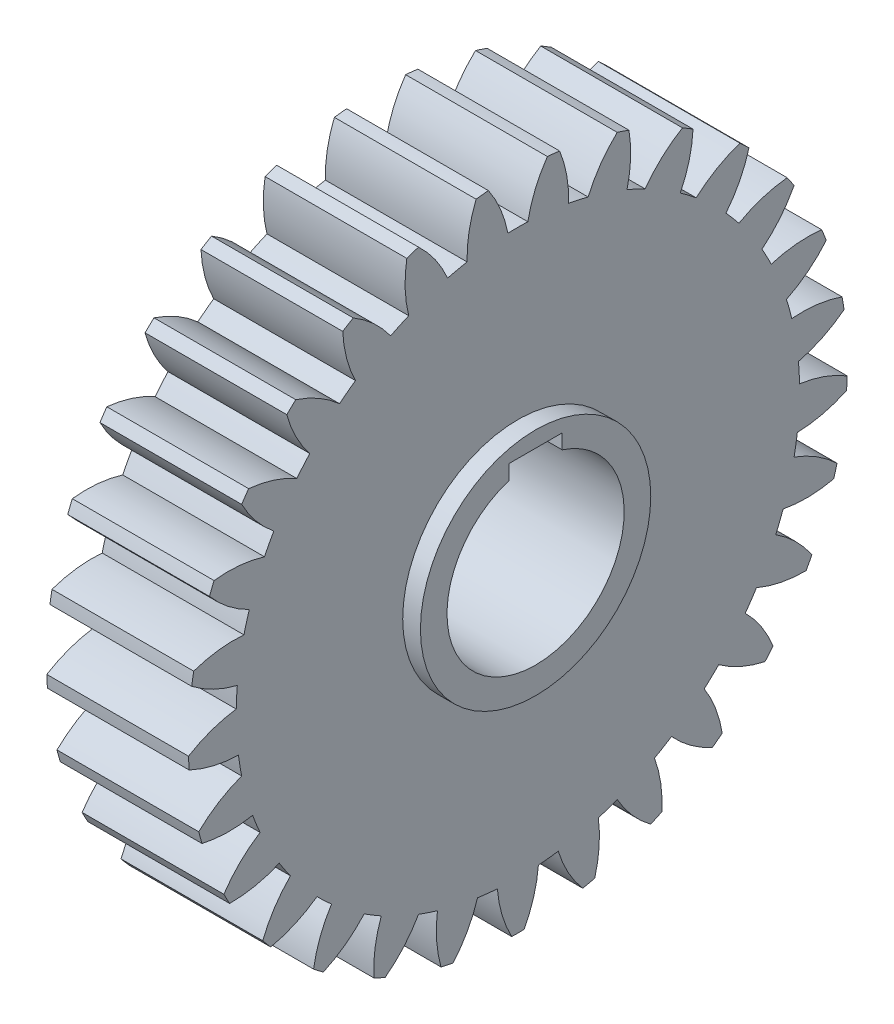
SolidWorks part; units mm, degrees
ref_plane "Plane1" through (0, 0, 0) normal (0, 0, 1) x (1, 0, 0)
ref_plane "Plane2" through (0, 0, 0) normal (0, 1, 0) x (1, 0, 0)
ref_plane "Plane3" through (0, 0, 0) normal (1, 0, 0) x (0, 0, -1)
sketch "HoldingSke" plane through (0, 0, 0) normal (0, 1, 0) x (1, 0, 0)
  line L0 (0, 0) -> (1.4577, -0.808)
  line L1 (-15, 0) -> (100, 0) construction
  line L2 (0, 0) -> (-2.1039, 2.3779)
  line L3 (0, 0) -> (-11.863, 4.5341)
  line L4 (0, 0) -> (7.5532, 4.1868)
  line L5 (0, 0) -> (-46.8476, -17.4728)
  line L6 (0, 0) -> (-3.3159, -2.2372)
  line L7 (-2.1039, 2.3779) -> (8.6586, 51.2059)
  line L8 (-76.2, 54.61) -> (-75.3, 54.61)
  line L9 (-71.009, 38.7566) -> (-53.1078, 45.2721)
  line L10 (-76.2, 71.12) -> (104.1128, 71.12)
  line L11 (0, 0) -> (-4, 0)
  line L12 (-76.2, 101.6) -> (-76.177, 101.6)
  line L13 (24.9733, 27.94) -> (52.9518, 28.4284)
  line L14 (24.9733, 27.94) -> (24.9743, 27.94)
  line L15 (24.9733, 27.94) -> (100.4006, 29.5858)
  line L16 (-63.627, -0.6) -> (-12.827, -0.6)
  circle A0 centre (0, 0) radius 2.5
  circle A1 centre (0, 0) radius 7.949
  circle A2 centre (0, 0) radius 37.5
  circle A3 centre (0, 0) radius 2.5
  dimension "MHD" = 15.898
  dimension "Hub_dia" = 75
  dimension "Bore" = 5
  dimension "MBD" = 5
  dimension "Num_teeth" = 29
  dimension "Pitch_radius" = 180.3128
  dimension "Pitch" = 1.6667
  dimension "Width" = 4
  dimension "Overall_len" = 50
  dimension "Show_teeth" = 29
  dimension "Thickness" = 4
  dimension "OAL" = 50.0001
  dimension "T_dim" = 0.9
  dimension "Ap" = 20
  dimension "H" = 19.05
  dimension "Backlash" = 0.023
  dimension "Addendum_fac" = 1
  dimension "Dedendum_fac" = 1.25
  dimension "Clearance_fac" = 0.25
  dimension "Dedendum_add" = 0.001
  dimension "Module" = 0.6
sketch "BasProSke" plane through (0, 0, 0) normal (0, 1, 0) x (1, 0, 0)
  line L0 (-10, 0) -> (60, 0) construction
  line L1 (0, 0) -> (0, 9.3)
  line L2 (0, 0) -> (4, 0)
  line L3 (4, 0) -> (4, 9.3)
  line L4 (4, 9.3) -> (0, 9.3)
  dimension "Diameter" = 18.6
  dimension "Thickness" = 4
revolve "Base-Revolve" add sketch "BasProSke" angle 360 about L0
sketch "TooCutSke" plane through (0, 0, 0) normal (1, 0, 0) x (0, 0, -1)
  line L1 (0, 0) -> (0, 107) construction
  line L2 (0, 0) -> (-0.5112, 8.685) construction
  line L3 (0, 0) -> (-1.879, 17.2768) construction
  line L4 (-0.5112, 8.685) -> (-0.9395, 8.6384) construction
  arc A0 (0.2815, 7.944) -> (-0.2815, 7.944) centre (0, 0) ccw
  arc A1 (0.8491, 9.2867) -> (-0.8491, 9.2867) centre (0, 0) ccw
  circle A2 centre (0, 0) radius 8.7 construction
  circle A3 centre (0, 0) radius 8.1753 construction
  arc A4 (-0.2815, 7.944) -> (-0.8491, 9.2867) centre (-3.6996, 7.2903) ccw
  arc A5 (0.8491, 9.2867) -> (0.2815, 7.944) centre (3.6996, 7.2903) ccw
  dimension "Root_dia" = 15.898
  dimension "Overcut_dia" = 18.6508
  dimension "Pitch_dia" = 17.4
  dimension "Base_dia" = 16.3507
  dimension "Flank_rad" = 3.48
  dimension "Half_ang" = 6.207
  dimension "Half_CT" = 0.4308
extrude "ToothCut" cut sketch "TooCutSke" along normal through all
fillet "Breaks" [suppressed] radius 0.012 tangent propagation no
fillet "RootFillets" [suppressed] radius 0.151
pattern_circular "TeethCuts" count 29 every 12.414 about axis through (-10, 0, 0) along (1, 0, 0) of "ToothCut", "RootFillets", "Breaks"
sketch "HubNeaOneSke" plane through (0, 0, 0) normal (-1, 0, 0) x (0, 0, 1)
  circle A0 centre (0, 0) radius 7.949
  dimension "Diameter" = 15.898
extrude "HubNearOne" [suppressed] add sketch "HubNeaOneSke" along normal blind 46.0001
sketch "HubNeaBotSke" plane through (0, 0, 0) normal (-1, 0, 0) x (0, 0, 1)
  circle A0 centre (0, 0) radius 7.949
  dimension "Diameter" = 15.898
extrude "HubNearBoth" [suppressed] add sketch "HubNeaBotSke" along normal blind 23
ref_plane "FarPln" through (4, 0, 0) normal (1, 0, 0) x (0, 0, -1)
sketch "HubFarSke" plane through (4, 0, 0) normal (1, 0, 0) x (0, 0, -1)
  circle A0 centre (0, 0) radius 7.949
  dimension "Diameter" = 15.898
extrude "HubFar" [suppressed] add sketch "HubFarSke" along normal blind 23
sketch "BorSke" plane through (0, 0, 0) normal (1, 0, 0) x (0, 0, -1)
  circle A0 centre (0, 0) radius 2.5
  dimension "Diameter" = 5
extrude "Bore" cut sketch "BorSke" along normal mid plane 100.0001
sketch "KeySke" plane through (0, 0, 0) normal (1, 0, 0) x (0, 0, -1)
  line L0 (-1, 0) -> (-1, 3.4)
  line L1 (-1, 3.4) -> (1, 3.4)
  line L2 (1, 3.4) -> (1, 0)
  line L3 (0, 0) -> (0, 34) construction
  line L4 (-1, 0) -> (1, 0)
  dimension "Offset" = 3.4
  dimension "Width" = 2
extrude "Keyway" [suppressed] cut sketch "KeySke" along normal mid plane 100.0001
pattern_circular "Keyway2" [suppressed] count 2 every 90 about axis through (-10, 0, 0) along (1, 0, 0)
sketch "Sketch1" plane through (0, 0, 0) normal (1, 0, 0) x (0, 0, -1)
  circle A0 centre (0, 0) radius 3.25
  circle A1 centre (0, 0) radius 2.5 construction
  circle A2 centre (0, 0) radius 2.5
  dimension "D1" = 6.5
extrude "Extrude1" add sketch "Sketch1" along normal blind 4.5 and the other way blind 0.5
sketch "Sketch2" plane through (0, 0, 0) normal (1, 0, 0) x (0, 0, -1)
  line L0 (0, 3.5365) -> (0, -1.3362) construction
  line L1 (-0.75, 2.8) -> (0.75, 2.8)
  line L2 (-0.75, 2.8) -> (-0.75, 0)
  line L3 (-0.75, 0) -> (0.75, 0)
  line L4 (0.75, 2.8) -> (0.75, 0)
  dimension "D1" = 2.8
  dimension "D2" = 1.5
extrude "Cut-Extrude1" cut sketch "Sketch2" against normal through all and the other way blind 20
equation "' \"Module@HoldingSke\" = 6.35"
equation "' \"Num_teeth@HoldingSke\" = 12"
equation "' \"Ap@HoldingSke\" =  20"
equation "' \"Width@HoldingSke\" = 0.5 * 25.4"
equation "' \"Hub_dia@HoldingSke\"= 1 * 25.4"
equation "' \"Overall_len@HoldingSke\" = 1.0 * 25.4"
equation "' \"Bore@HoldingSke\" = 0.75 * 25.4"
equation "' \"T_dim@HoldingSke\" = 0.1 * 25.4"
equation "' \"Width@KeySke\" = 0.25 * 25.4"
equation "' \"Show_teeth@HoldingSke\" = 13"
equation "' \"Backlash@HoldingSke\" = 0.009 * 25.4"
equation "' \"Addendum_fac@HoldingSke\" = 1.0"
equation "' \"Dedendum_fac@HoldingSke\" = 1.25"
equation "' \"Dedendum_add@HoldingSke\" = 0.00005 * 25.4"
equation "' \"Clearance_fac@HoldingSke\" = 0.25"
equation "\"Pitch@HoldingSke\" = 1 / \"Module@HoldingSke\""
equation "\"Overcut_dia@TooCutSke\" = (\"Num_teeth@HoldingSke\" + 2 * \"Addendum_fac@HoldingSke\") / \"Pitch@HoldingSke\" + 0.002 * 25.4"
equation "\"Pitch_dia@TooCutSke\" = \"Num_teeth@HoldingSke\" / \"Pitch@HoldingSke\""
equation "\"Base_dia@TooCutSke\" = \"Num_teeth@HoldingSke\" / \"Pitch@HoldingSke\" * cos((\"Ap@HoldingSke\"  * 3.14159265 / 180))"
equation "\"Root_dia@TooCutSke\" = (\"Num_teeth@HoldingSke\" + 2) / \"Pitch@HoldingSke\" - 2 * (\"Addendum_fac@HoldingSke\" + \"Dedendum_fac@HoldingSke\") / \"Pitch@HoldingSke\" - \"Dedendum_add@HoldingSke\" * 2"
equation "\"Half_ang@TooCutSke\" = 180 / \"Num_teeth@HoldingSke\""
equation "\"Half_CT@TooCutSke\" = \"Num_teeth@HoldingSke\" / \"Pitch@HoldingSke\" * sin((3.14159265 / 2 / \"Num_teeth@HoldingSke\")) / 2 - 7 * \"Backlash@HoldingSke\" / 4"
equation "\"Flank_rad@TooCutSke\" = \"Num_teeth@HoldingSke\" / \"Pitch@HoldingSke\" / 5"
equation "\"Radius@RootFillets\" = \"Clearance_fac@HoldingSke\" / \"Pitch@HoldingSke\" + \"Dedendum_add@HoldingSke\""
equation "\"Break_rad@Breaks\" = 0.02 / \"Pitch@HoldingSke\""
equation "\"Thickness@HoldingSke\" = \"Width@HoldingSke\""
equation "\"OAL@HoldingSke\" = \"Thickness@HoldingSke\""
equation "\"MHD@HoldingSke\" = (\"Num_teeth@HoldingSke\" + 2) / \"Pitch@HoldingSke\" - 2 * (\"Addendum_fac@HoldingSke\" + \"Dedendum_fac@HoldingSke\")  / \"Pitch@HoldingSke\" - \"Dedendum_add@HoldingSke\" * 2"
equation "\"MBD@HoldingSke\" = (\"Num_teeth@HoldingSke\" + 2) / \"Pitch@HoldingSke\" - 2 * (\"Addendum_fac@HoldingSke\" + \"Dedendum_fac@HoldingSke\")  / \"Pitch@HoldingSke\" - \"Dedendum_add@HoldingSke\" * 2 - 0.002 * 25.4"
equation "\"MHD@HoldingSke\" = ((sgn( \"MHD@HoldingSke\" - \"Hub_dia@HoldingSke\" )-1)*( \"MHD@HoldingSke\" - \"Hub_dia@HoldingSke\" ))/-2+ \"Hub_dia@HoldingSke\""
equation "\"MBD@HoldingSke\" = ((sgn( \"MBD@HoldingSke\" - \"Bore@HoldingSke\" )-1)*( \"MBD@HoldingSke\" - \"Bore@HoldingSke\" ))/-2+ \"Bore@HoldingSke\""
equation "\"OAL@HoldingSke\" = ((sgn( \"OAL@HoldingSke\" - \"Overall_len@HoldingSke\" )+1)*( \"OAL@HoldingSke\" - \"Overall_len@HoldingSke\" ))/2 + \"Overall_len@HoldingSke\" + 0.000002 * 25.4"
equation "\"Num_teeth@TeethCuts\" = int( \"Show_teeth@HoldingSke\" ) + 1"
equation "\"Num_teeth@TeethCuts\" = ((sgn( \"Num_teeth@TeethCuts\" - \"Num_teeth@HoldingSke\" )-1)*( \"Num_teeth@TeethCuts\" - \"Num_teeth@HoldingSke\" ))/-2+ \"Num_teeth@HoldingSke\""
equation "\"Num_teeth@TeethCuts\" = ((sgn( \"Num_teeth@TeethCuts\" - 2.0)+1)*( \"Num_teeth@TeethCuts\" - 2.0))/2 +2.0"
equation "\"Angle@TeethCuts\" = 360.0 / \"Num_teeth@HoldingSke\""
equation "\"Diameter@BasProSke\" = (\"Num_teeth@HoldingSke\" + 2 * \"Addendum_fac@HoldingSke\") / \"Pitch@HoldingSke\""
equation "\"Thickness@BasProSke\"  = \"Thickness@HoldingSke\""
equation "' \"Fillet_rad@BasProSke\" =  \"Thickness@HoldingSke\" * 0.05"
equation "\"MHD@HoldingSke\" = ((sgn( \"MHD@HoldingSke\" - \"Root_dia@TooCutSke\" )-1)*( \"MHD@HoldingSke\" - \"Root_dia@TooCutSke\" ))/-2+ \"Root_dia@TooCutSke\""
equation "\"Diameter@HubNeaOneSke\" = \"MHD@HoldingSke\""
equation "\"Length@HubNearOne\" = \"OAL@HoldingSke\" - \"Thickness@BasProSke\""
equation "\"Diameter@HubNeaBotSke\" = \"MHD@HoldingSke\""
equation "\"Length@HubNearBoth\" = ( \"OAL@HoldingSke\" - \"Thickness@BasProSke\" ) / 2.0"
equation "\"Thickness@FarPln\" = \"Thickness@BasProSke\""
equation "\"Diameter@HubFarSke\" = \"MHD@HoldingSke\""
equation "\"Length@HubFar\" = ( \"OAL@HoldingSke\" - \"Thickness@BasProSke\" ) / 2.0"
equation "\"Diameter@BorSke\" = \"MBD@HoldingSke\""
equation "\"D1@Bore\" = \"OAL@HoldingSke\" * 2.0"
equation "\"D1@Keyway\" = \"OAL@HoldingSke\" * 2.0"
equation "\"Offset@KeySke\" = \"T_dim@HoldingSke\" + \"MBD@HoldingSke\" / 2.0"
